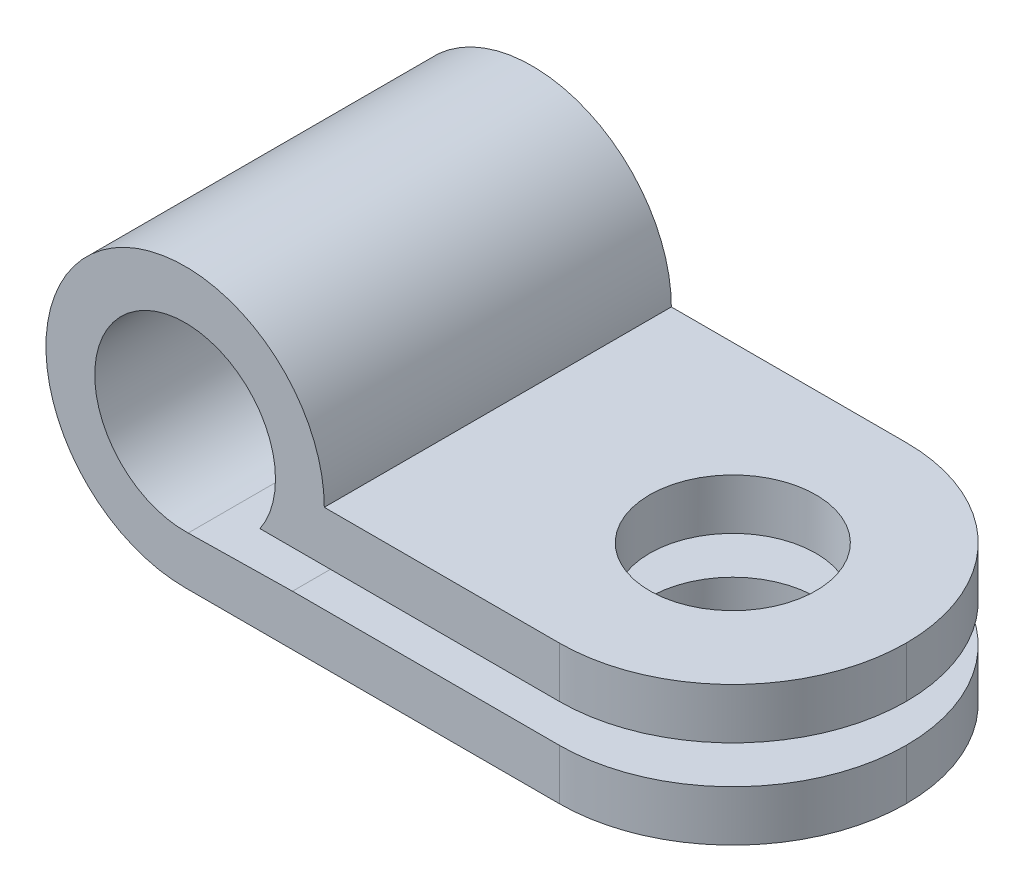
SolidWorks part; units mm, degrees
material "Nylon 101"
ref_plane "Front Plane" through (0, 0, 0) normal (0, 0, 1) x (1, 0, 0)
ref_plane "Top Plane" through (0, 0, 0) normal (0, 1, 0) x (1, 0, 0)
ref_plane "Right Plane" through (0, 0, 0) normal (1, 0, 0) x (0, 0, -1)
sketch "Sketch1" plane through (0, 0, 0) normal (0, 0, 1) x (1, 0, 0)
  line L0 (0, -3.85) -> (15.15, -3.85)
  line L1 (15.15, -3.85) -> (15.15, -2.45)
  line L2 (15.15, -2.45) -> (2.9698, -2.45)
  line L3 (15.15, -1.4) -> (2.0712, -1.4)
  line L4 (15.15, 0) -> (3.85, 0)
  line L5 (15.15, 0) -> (15.15, -1.4)
  line L6 (2.9698, -2.45) -> (0, -2.5)
  arc A0 (2.5, 0) -> (2.0712, -1.4) centre (0, 0) cw
  arc A1 (2.5, 0) -> (0.0842, -2.4986) centre (0, 0) ccw
  arc A2 (3.85, 0) -> (0, -3.85) centre (0, 0) ccw
  dimension "D1" = 19
  dimension "D2" = 5
  dimension "D3" = 1.4
extrude "Boss-Extrude1" add sketch "Sketch1" along normal blind 9.6 contours L4 A2 L0 L1 L2 L6 A1 A0 L3 L5 region at (5.1239, -1.1043, 0)
fillet "Fillet1" radius 4.8 4 edges at (15.15, -0.7, 0) (15.15, -0.7, 9.6) (15.15, -3.15, 0) (15.15, -3.15, 9.6)
sketch "Sketch2" plane through (0, 0, 0) normal (0, 1, 0) x (1, 0, 0)
  circle A0 centre (10.35, -4.8) radius 2.3
  arc A1 (15.15, -4.8) -> (10.35, 0) centre (10.35, -4.8) ccw construction
  dimension "D1" = 4.6
extrude "Cut-Extrude1" cut sketch "Sketch2" against normal blind 10
